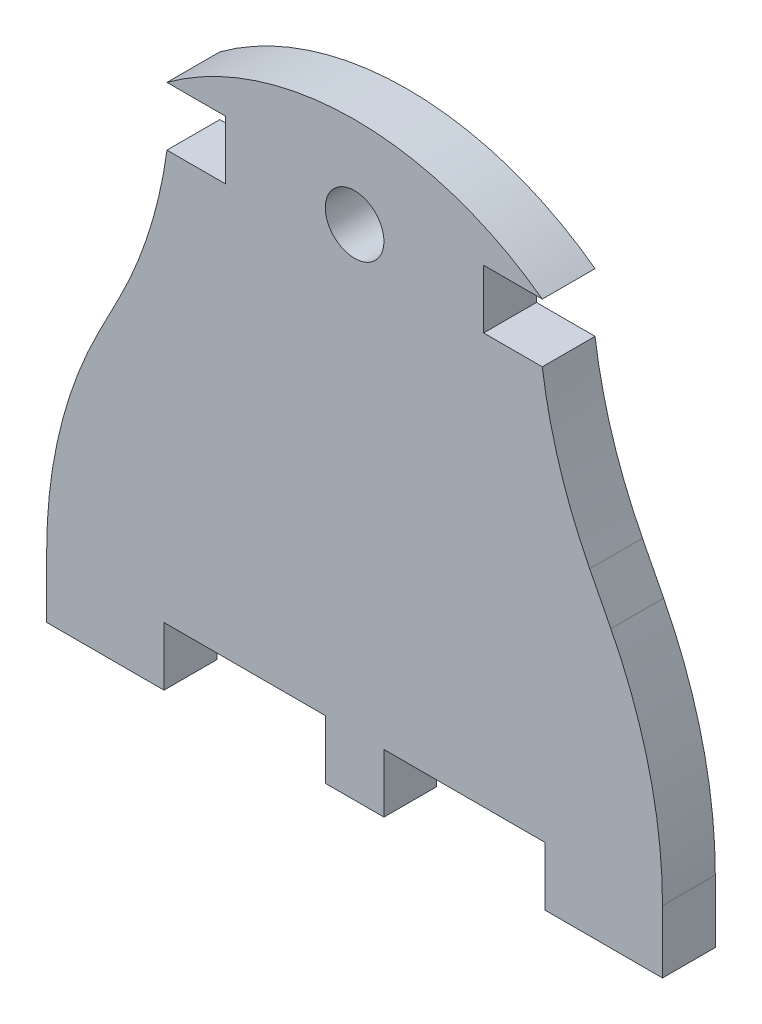
SolidWorks part; units mm, degrees
material "Balsa"
ref_plane "Front Plane" through (0, 0, 0) normal (0, 0, 1) x (1, 0, 0)
ref_plane "Top Plane" through (0, 0, 0) normal (0, 1, 0) x (1, 0, 0)
ref_plane "Right Plane" through (0, 0, 0) normal (1, 0, 0) x (0, 0, -1)
sketch "Sketch1" plane through (0, 0, 0) normal (0, 0, 1) x (1, 0, 0)
  line L0 (0, 0) -> (0, 61.7042) construction
  line L1 (-26.25, 15.7042) -> (-26.25, 25.7042)
  line L2 (-26.25, 10.7042) -> (-16.25, 10.7042)
  line L3 (-26.25, 10.7042) -> (-26.25, 15.7042)
  line L4 (-26.25, 15.7042) -> (-16.25, 15.7042)
  line L5 (-16.25, 10.7042) -> (-16.25, 15.7042)
  line L6 (-26.25, 25.7042) -> (-16, 45.7042)
  line L7 (-16, 45.7042) -> (-16, 50.7042)
  line L8 (-16, 50.7042) -> (-11, 50.7042)
  line L9 (-11, 50.7042) -> (-11, 55.7042)
  line L10 (-11, 55.7042) -> (-16, 55.7042)
  line L11 (-16, 55.7042) -> (-16, 63.7042)
  line L12 (16, 55.7042) -> (16, 63.7042)
  line L13 (11, 55.7042) -> (16, 55.7042)
  line L14 (11, 50.7042) -> (11, 55.7042)
  line L15 (16, 50.7042) -> (11, 50.7042)
  line L16 (16, 45.7042) -> (16, 50.7042)
  line L17 (26.25, 25.7042) -> (16, 45.7042)
  line L18 (16.25, 10.7042) -> (16.25, 15.7042)
  line L19 (26.25, 15.7042) -> (16.25, 15.7042)
  line L20 (26.25, 10.7042) -> (26.25, 15.7042)
  line L21 (26.25, 10.7042) -> (16.25, 10.7042)
  line L22 (26.25, 15.7042) -> (26.25, 25.7042)
  line L23 (-16.25, 15.7042) -> (16.25, 15.7042)
  line L24 (15.8745, 61.7042) -> (-15.8745, 61.7042)
  line L25 (-15.8745, 61.7042) -> (-16, 61.7042)
  line L26 (15.8745, 61.7042) -> (16, 61.7042)
  arc A0 (16, 63.7042) -> (-16, 63.7042) centre (0, 63.7042) ccw
  circle A2 centre (0, 53.2124) radius 2.5
  dimension "D11" = 5
  dimension "D1" = 10
  dimension "D2" = 5
  dimension "D3" = 26.25
  dimension "D4" = 20
  dimension "D5" = 16
  dimension "D6" = 5
  dimension "D7" = 5
  dimension "D8" = 5
  dimension "D9" = 5
  dimension "D10" = 8
  dimension "D12" = 6
  dimension "D13" = 10
extrude "Boss-Extrude1" add sketch "Sketch1" along normal blind 4.5 contours L0 L23 L19 L22 L17 L16 L15 L14 L13 L12 A0 L24 A2 | L23 L0 A2 L24 A0 L11 L10 L9 L8 L7 L6 L1 L4 | L21 L20 L19 L18 | L2 L5 L4 L3 region at (-10.6994, 35.3946, 0) region at (10.6994, 35.3946, 0) region at (-21.25, 13.2042, 0) region at (21.25, 13.2042, 0)
fillet "Fillet1" radius 40 4 edges at (-16, 45.7042, 2.25) (-26.25, 25.7042, 2.25) (16, 45.7042, 2.25) (26.25, 25.7042, 2.25)
sketch "Sketch2" plane through (0, 15.7042, 0) normal (0, -1, 0) x (1, 0, 0)
  line L0 (-16.25, 2.25) -> (16.25, 2.25) construction
  line L1 (-16.25, 4.5) -> (-16.25, 0) construction
  line L2 (16.25, 4.5) -> (16.25, 0) construction
  line L3 (-16.25, 4.5) -> (16.25, 4.5) construction
  line L4 (-2.5, 0) -> (2.5, 0)
  line L5 (-2.5, 0) -> (-2.5, 4.5)
  line L6 (-2.5, 4.5) -> (2.5, 4.5)
  line L7 (2.5, 0) -> (2.5, 4.5)
  line L8 (-2.5, 0) -> (2.5, 4.5) construction
  line L9 (-2.5, 4.5) -> (2.5, 0) construction
  point P6 (0, 2.25)
  dimension "D1" = 5
extrude "Boss-Extrude2" add sketch "Sketch2" along normal blind 5
chamfer "Chamfer1" distance 6 angle 45 2 edges at (16, 61.7042, 2.25) (-16, 61.7042, 2.25)
fillet "Fillet2" radius 30 2 edges at (10, 61.7042, 2.25) (-10, 61.7042, 2.25)
sketch "Sketch3" plane through (0, 0, 4.5) normal (0, 0, 1) x (1, 0, 0)
  arc A0 (-16, 55.7042) -> (16, 55.7042) centre (0, 33.9911) cw
  arc A1 (16, 55.7042) -> (-16, 55.7042) centre (0, 53.0203) ccw
extrude "Cut-Extrude1" cut sketch "Sketch3" against normal blind 10
